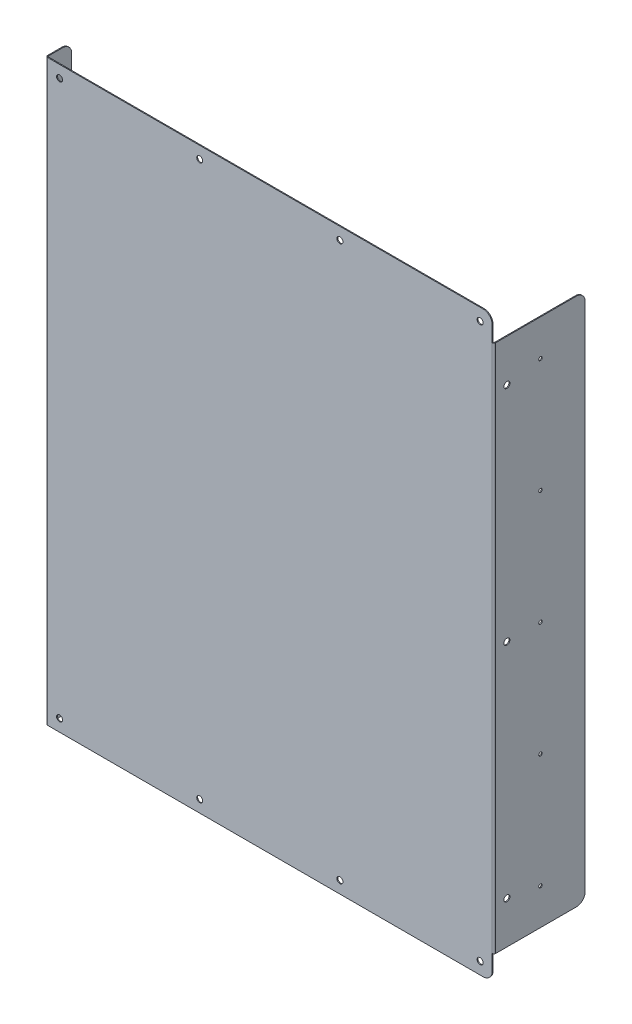
SolidWorks part; units mm, degrees
note: The reader was unsure of these and kept them because the rebuilt part matched: bend radius of "BaseBend1", "BaseBend2".
ref_plane "Front Plane" through (0, 0, 0) normal (0, 0, 1) x (1, 0, 0)
ref_plane "Top Plane" through (0, 0, 0) normal (0, 1, 0) x (1, 0, 0)
ref_plane "Right Plane" through (0, 0, 0) normal (1, 0, 0) x (0, 0, -1)
sketch "Sketch1" plane through (0, 0, 0) normal (0, 1, 0) x (1, 0, 0)
  line L0 (-370.5, 0) -> (370.5, 0)
  line L1 (370.5, 0) -> (370.5, 150)
  line L3 (-370.5, 0) -> (-370.5, 40)
  dimension "D1" = 40
  dimension "D2" = 741
  dimension "D3" = 150
base flange "Base-Flange1" sketch "Sketch1" end condition mid plane depth 960 reverse direction no thickness 1.5 reverse thickness direction yes bend radius 1.5
bend "BaseBend1" bend radius 1.5 bend angle 90 parameters "D5"=1
bend "BaseBend2" bend radius 1.5 bend angle 90 parameters "D5"=2
sketch "Sketch6" plane through (372, 0, 0) normal (1, 0, 0) x (0, 0, -1)
  line L0 (150, 480) -> (1.5, 480) construction
  line L1 (-11.5, 480) -> (158.5, 480)
  line L2 (-11.5, 480) -> (-11.5, 439)
  line L3 (-11.5, 439) -> (158.5, 439)
  line L4 (158.5, 480) -> (158.5, 439)
  line L5 (-1.5, 480) -> (-1.5, -480) construction
  dimension "D1" = 41
  dimension "D2" = 10
  dimension "D3" = 170
extrude "Cut-Extrude1" cut sketch "Sketch6" against normal up to vertex (3 mm away) and the other way through all normal cut yes up to point (369, 480, 1.5)
mirror "Mirror1" about plane through (0, 0, 0) normal (0, 1, 0) of "Cut-Extrude1"
hole_wizard "M5 Clearance Hole1" positions "Sketch7" profile "Sketch8" hole size "M5" standard "ISO" end condition through all
sketch "Sketch7" plane through (372, 0, 0) normal (1, 0, 0) x (0, 0, -1)
  line L0 (75.75, -379) -> (75.75, -189.5) construction
  line L1 (75.75, -189.5) -> (75.75, 0) construction
  line L2 (75.75, 0) -> (75.75, 189.5) construction
  line L3 (75.75, 189.5) -> (75.75, 379) construction
  line L4 (75.75, 379) -> (75.75, 439) construction
  line L5 (1.5, 439) -> (150, 439) construction
  line L7 (0, 0) -> (75.75, 0) construction
  point P0 (75.75, 379)
  point P2 (75.75, 189.5)
  point P4 (75.75, 0)
  point P6 (75.75, -189.5)
  point P8 (75.75, -379)
  dimension "D1" = 60
sketch "Sketch8" plane through (372, 379, -75.75) normal (0, 1, 0) x (0, 0, -1)
  line L0 (0, 0) -> (0, 744)
  line L1 (0, 744) -> (2.9, 744)
  line L2 (2.9, 744) -> (2.9, 0)
  line L5 (2.9, 0) -> (0, 0)
  line L11 (0, -6.35) -> (0, 107.95) construction
  dimension "Thru Hole Dia." = 5.8
  dimension "Thru Hole Depth" = 744
fillet "Fillet1" radius 15 6 edges at (371.25, -439, -150) (369, -480, 0.75) (371.25, 439, -150) (369, 480, 0.75) (-371.25, -480, -40) (-371.25, 480, -40)
hole_wizard "M8 Clearance Hole1" positions "Sketch9" profile "Sketch10" hole size "M8" standard "ISO" end condition through all
sketch "Sketch9" plane through (0, 0, 1.5) normal (0, 0, 1) x (1, 0, 0)
  line L0 (369, 460) -> (349, 460) construction
  line L1 (369, 465) -> (369, 439) construction
  line L2 (349, 460) -> (116.3333, 460) construction
  line L3 (116.3333, 460) -> (-116.3333, 460) construction
  line L4 (-116.3333, 460) -> (-349, 460) construction
  line L5 (-349, 460) -> (-369, 460) construction
  line L6 (-369, 480) -> (-369, -480) construction
  line L8 (354, 480) -> (-369, 480) construction
  point P0 (349, 460)
  point P2 (116.3333, 460)
  point P4 (-116.3333, 460)
  point P6 (-349, 460)
  dimension "D1" = 20
  dimension "D2" = 20
sketch "Sketch10" plane through (349, 460, 1.5) normal (1, 0, 0) x (0, -1, 0)
  line L0 (0, 0) -> (0, 151.5)
  line L1 (0, 151.5) -> (5, 151.5)
  line L2 (5, 151.5) -> (5, 0)
  line L5 (5, 0) -> (0, 0)
  line L11 (0, -6.35) -> (0, 107.95) construction
  dimension "Thru Hole Dia." = 10
  dimension "Thru Hole Depth" = 151.5
mirror "Mirror2" about plane through (0, 0, 0) normal (0, 1, 0) of "M8 Clearance Hole1"
hole_wizard "M8 Clearance Hole2" positions "Sketch11" profile "Sketch13" hole size "M8" standard "ISO"
sketch "Sketch11" plane through (-372, 0, 0) normal (-1, 0, 0) x (0, 0, 1)
  line L0 (-20, 480) -> (-20, 410) construction
  line L1 (-1.5, 480) -> (-25, 480) construction
  line L2 (-20, 410) -> (-20, 136.6667) construction
  line L3 (-20, 136.6667) -> (-20, -136.6667) construction
  line L4 (-20, -136.6667) -> (-20, -410) construction
  line L6 (-20, -480) -> (-20, -410) construction
  line L7 (-1.5, -480) -> (-25, -480) construction
  point P0 (-20, 410)
  point P2 (-20, 136.6667)
  point P4 (-20, -136.6667)
  point P6 (-20, -410)
  dimension "D1" = 20
  dimension "D2" = 70
sketch "Sketch13" plane through (-372, 410, -20) normal (0, 1, 0) x (0, 0, 1)
  line L0 (0, 0) -> (0, 12)
  line L1 (0, 12) -> (5, 8.9957)
  line L2 (5, 8.9957) -> (5, 0)
  line L5 (5, 0) -> (0, 0)
  line L10 (0, 12) -> (-5, 8.9957) construction
  line L11 (0, -6.35) -> (0, 107.95) construction
  dimension "Hole Dia." = 10
  dimension "Hole Depth" = 12
  dimension "Drill Angle" = 118
hole_wizard "M8 Clearance Hole3" positions "Sketch14" profile "Sketch15" hole size "M8" standard "ISO"
sketch "Sketch14" plane through (372, 0, 0) normal (1, 0, 0) x (0, 0, -1)
  line L0 (20, 439) -> (20, 369) construction
  line L1 (1.5, 439) -> (135, 439) construction
  line L2 (20, 369) -> (20, 0) construction
  line L3 (20, 0) -> (20, -369) construction
  line L4 (20, -369) -> (20, -439) construction
  line L5 (1.5, -439) -> (135, -439) construction
  line L7 (0, 439) -> (0, -439) construction
  point P0 (20, 369)
  point P2 (20, 0)
  point P4 (20, -369)
  dimension "D1" = 70
  dimension "D2" = 20
sketch "Sketch15" plane through (372, 369, -20) normal (0, 1, 0) x (0, 0, -1)
  line L0 (0, 0) -> (0, 12)
  line L1 (0, 12) -> (5, 8.9957)
  line L2 (5, 8.9957) -> (5, 0)
  line L5 (5, 0) -> (0, 0)
  line L10 (0, 12) -> (-5, 8.9957) construction
  line L11 (0, -6.35) -> (0, 107.95) construction
  dimension "Hole Dia." = 10
  dimension "Hole Depth" = 12
  dimension "Drill Angle" = 118
sketch "Bend-Lines1" [suppressed] plane through (0, 0, 0) normal (0, 1, 0) x (1, 0, 0)
sketch "Bounding-Box1" [suppressed] plane through (0, 0, 0) normal (0, 1, 0) x (1, 0, 0)
sheet metal parameters "Sheet-Metal1" thickness 1.5 parameters "D1"=1.5
flat pattern "Flat-Pattern1" [suppressed]
sketch "Bend-Lines2" plane through (0, 0, 1.5) normal (0, 0, 1) x (1, 0, 0)
  line L0 (519.3014, 480) -> (519.3014, -480) construction
  line L1 (370.2671, 480) -> (370.2671, -480) construction
  line L2 (-370.2671, -480) -> (-370.2671, 480) construction
  line L3 (519.3014, 480) -> (519.3014, -480) construction
  line L4 (370.2671, 480) -> (370.2671, -480) construction
  line L5 (-370.2671, -480) -> (-370.2671, 480) construction
sketch3d "Bounding-Box2" [suppressed]
  line L0 (913.0686, 0, 0) -> (913.0686, -960, 0) construction
  line L1 (-40.5343, 0, 0) -> (-40.5343, -960, 0) construction
  line L2 (913.0686, 0, 0) -> (-40.5343, 0, 0) construction
  line L3 (913.0686, -960, 0) -> (-40.5343, -960, 0) construction
bend of the flat pattern "Flatten-<BaseBend1>1"
bend of the flat pattern "Flatten-<BaseBend2>1"
sheet metal parameters "Sheet-Metal2" thickness 1.5 parameters "D1"=1.5
flat pattern "Flat-Pattern1"
sketch "Bend-Lines2" plane through (0, 0, 1.5) normal (0, 0, 1) x (1, 0, 0)
  line L0 (519.3014, 439) -> (519.3014, -480) construction
  line L1 (370.2671, 439) -> (370.2671, -480) construction
  line L2 (-370.2671, -480) -> (-370.2671, 480) construction
  line L3 (519.3014, 439) -> (519.3014, -480) construction
  line L4 (370.2671, 439) -> (370.2671, -480) construction
  line L5 (-370.2671, -480) -> (-370.2671, 480) construction
sketch3d "Bounding-Box2" [suppressed]
  line L0 (913.0686, 0, 0) -> (913.0686, -960, 0) construction
  line L1 (-40.5343, 0, 0) -> (-40.5343, -960, 0) construction
  line L2 (913.0686, 0, 0) -> (-40.5343, 0, 0) construction
  line L3 (913.0686, -960, 0) -> (-40.5343, -960, 0) construction
bend of the flat pattern "Flatten-<BaseBend1>1"
bend of the flat pattern "Flatten-<BaseBend2>1"
sheet metal parameters "Sheet-Metal3" thickness 1.5 parameters "D1"=1.5
flat pattern "Flat-Pattern1"
sketch "Bend-Lines2" plane through (0, 0, 1.5) normal (0, 0, 1) x (1, 0, 0)
  line L0 (519.3014, 439) -> (519.3014, -439) construction
  line L1 (370.2671, 439) -> (370.2671, -439) construction
  line L2 (-370.2671, -480) -> (-370.2671, 480) construction
  line L3 (519.3014, 439) -> (519.3014, -439) construction
  line L4 (370.2671, 439) -> (370.2671, -439) construction
  line L5 (-370.2671, -480) -> (-370.2671, 480) construction
sketch3d "Bounding-Box2" [suppressed]
  line L0 (913.0686, 0, 0) -> (913.0686, -960, 0) construction
  line L1 (-40.5343, 0, 0) -> (-40.5343, -960, 0) construction
  line L2 (913.0686, 0, 0) -> (-40.5343, 0, 0) construction
  line L3 (913.0686, -960, 0) -> (-40.5343, -960, 0) construction
bend of the flat pattern "Flatten-<BaseBend1>1"
bend of the flat pattern "Flatten-<BaseBend2>1"
sheet metal parameters "Sheet-Metal4" thickness 1.5 parameters "D1"=1.5
flat pattern "Flat-Pattern1"
sketch "Bend-Lines2" plane through (0, 0, 1.5) normal (0, 0, 1) x (1, 0, 0)
  line L1 (370.7671, 439) -> (370.7671, -439) construction
  line L2 (-370.7671, -480) -> (-370.7671, 480) construction
  line L4 (370.7671, 439) -> (370.7671, -439) construction
  line L5 (-370.7671, -480) -> (-370.7671, 480) construction
sketch3d "Bounding-Box2" [suppressed]
  line L0 (891.5343, -960, 0) -> (891.5343, 0, 0) construction
  line L1 (-40.5343, -960, 0) -> (-40.5343, 0, 0) construction
  line L2 (891.5343, -960, 0) -> (-40.5343, -960, 0) construction
  line L3 (891.5343, 0, 0) -> (-40.5343, 0, 0) construction
bend of the flat pattern "Flatten-<BaseBend1>1"
bend of the flat pattern "Flatten-<BaseBend2>1"
sheet metal parameters "Sheet-Metal5" thickness 1.5 parameters "D1"=1.5
flat pattern "Flat-Pattern1"
sketch "Bend-Lines2" plane through (0, 0, 1.5) normal (0, 0, 1) x (1, 0, 0)
  line L1 (370.7671, 439) -> (370.7671, -439) construction
  line L2 (-370.7671, -480) -> (-370.7671, 480) construction
  line L4 (370.7671, 439) -> (370.7671, -439) construction
  line L5 (-370.7671, -480) -> (-370.7671, 480) construction
sketch3d "Bounding-Box2" [suppressed]
  line L0 (891.5343, -960, 0) -> (891.5343, 0, 0) construction
  line L1 (-40.5343, -960, 0) -> (-40.5343, 0, 0) construction
  line L2 (891.5343, -960, 0) -> (-40.5343, -960, 0) construction
  line L3 (891.5343, 0, 0) -> (-40.5343, 0, 0) construction
bend of the flat pattern "Flatten-<BaseBend1>1"
bend of the flat pattern "Flatten-<BaseBend2>1"
sheet metal parameters "Sheet-Metal6" thickness 1.5 parameters "D1"=1.5
flat pattern "Flat-Pattern1"
sketch "Bend-Lines2" plane through (0, 0, 1.5) normal (0, 0, 1) x (1, 0, 0)
  line L1 (370.7671, 439) -> (370.7671, -439) construction
  line L2 (-370.7671, -480) -> (-370.7671, 480) construction
  line L4 (370.7671, 439) -> (370.7671, -439) construction
  line L5 (-370.7671, -480) -> (-370.7671, 480) construction
sketch3d "Bounding-Box2" [suppressed]
  line L0 (891.5343, -960, 0) -> (891.5343, 0, 0) construction
  line L1 (-40.5343, -960, 0) -> (-40.5343, 0, 0) construction
  line L2 (891.5343, -960, 0) -> (-40.5343, -960, 0) construction
  line L3 (891.5343, 0, 0) -> (-40.5343, 0, 0) construction
bend of the flat pattern "Flatten-<BaseBend1>1"
bend of the flat pattern "Flatten-<BaseBend2>1"
sheet metal parameters "Sheet-Metal7" thickness 1.5 parameters "D1"=1.5
flat pattern "Flat-Pattern1"
sketch "Bend-Lines2" plane through (0, 0, 1.5) normal (0, 0, 1) x (1, 0, 0)
  line L1 (370.7671, 439) -> (370.7671, -439) construction
  line L2 (-370.7671, -480) -> (-370.7671, 480) construction
  line L4 (370.7671, 439) -> (370.7671, -439) construction
  line L5 (-370.7671, -480) -> (-370.7671, 480) construction
sketch3d "Bounding-Box2" [suppressed]
  line L0 (891.5343, -960, 0) -> (891.5343, 0, 0) construction
  line L1 (-40.5343, -960, 0) -> (-40.5343, 0, 0) construction
  line L2 (891.5343, -960, 0) -> (-40.5343, -960, 0) construction
  line L3 (891.5343, 0, 0) -> (-40.5343, 0, 0) construction
bend of the flat pattern "Flatten-<BaseBend1>1"
bend of the flat pattern "Flatten-<BaseBend2>1"
sheet metal parameters "Sheet-Metal8" thickness 1.5 parameters "D1"=1.5
flat pattern "Flat-Pattern1"
sketch "Bend-Lines2" plane through (0, 0, 1.5) normal (0, 0, 1) x (1, 0, 0)
  line L1 (370.7671, 439) -> (370.7671, -439) construction
  line L2 (-370.7671, -480) -> (-370.7671, 480) construction
  line L4 (370.7671, 439) -> (370.7671, -439) construction
  line L5 (-370.7671, -480) -> (-370.7671, 480) construction
sketch3d "Bounding-Box2" [suppressed]
  line L0 (891.5343, -960, 0) -> (891.5343, 0, 0) construction
  line L1 (-40.5343, -960, 0) -> (-40.5343, 0, 0) construction
  line L2 (891.5343, -960, 0) -> (-40.5343, -960, 0) construction
  line L3 (891.5343, 0, 0) -> (-40.5343, 0, 0) construction
bend of the flat pattern "Flatten-<BaseBend1>1"
bend of the flat pattern "Flatten-<BaseBend2>1"
